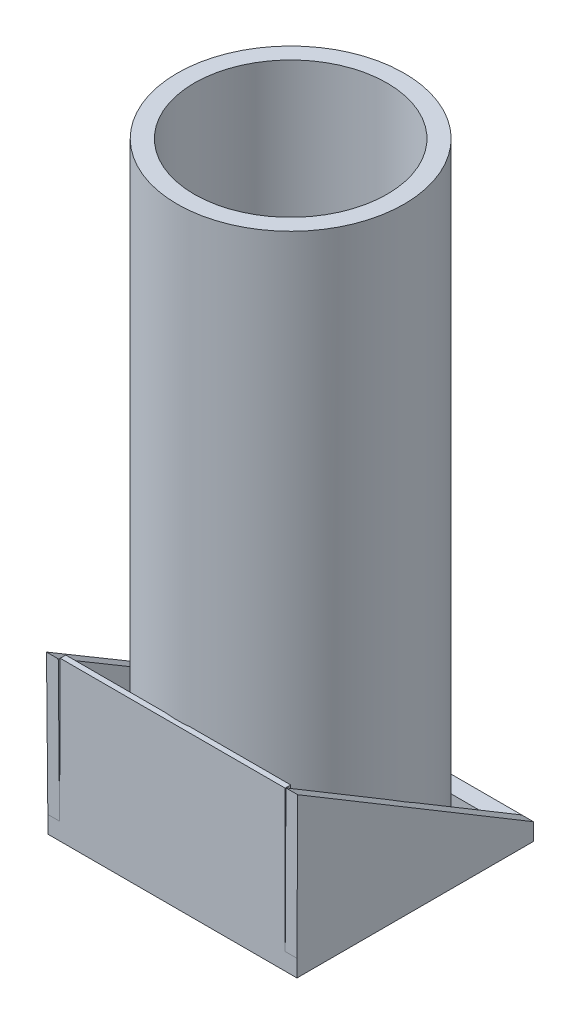
SolidWorks part; units mm, degrees
ref_plane "Front Plane" through (0, 0, 0) normal (0, 0, 1) x (1, 0, 0)
ref_plane "Top Plane" through (0, 0, 0) normal (0, 1, 0) x (1, 0, 0)
ref_plane "Right Plane" through (0, 0, 0) normal (1, 0, 0) x (0, 0, -1)
sketch "Sketch1" plane through (0, 0, 0) normal (0, 1, 0) x (1, 0, 0)
  circle A0 centre (0, 0) radius 135
  dimension "D1" = 270
extrude "Boss-Extrude1" add sketch "Sketch1" along normal blind 700
sketch "Sketch2" plane through (0, 0, 0) normal (0, -1, 0) x (-1, 0, 0)
  line L1 (-148.1806, 140.7055) -> (148.1806, 140.7055)
  line L2 (-148.1806, 140.7055) -> (-148.1806, -140.7055)
  line L3 (-148.1806, -140.7055) -> (148.1806, -140.7055)
  line L4 (148.1806, 140.7055) -> (148.1806, -140.7055)
  line L5 (-148.1806, 140.7055) -> (148.1806, -140.7055) construction
  line L6 (-148.1806, -140.7055) -> (148.1806, 140.7055) construction
  point P0 (0, 0)
extrude "Boss-Extrude2" add sketch "Sketch2" along normal blind 20.32
sketch "Sketch3" plane through (-148.1806, 0, 0) normal (-1, 0, 0) x (0, 0, 1)
  line L0 (-140.7055, 0) -> (142.3005, 168.1079)
  line L1 (142.3005, 168.1079) -> (140.7055, 0)
  line L2 (140.7055, 0) -> (-140.7055, 0)
  dimension "D1" = 168.1079
shell "Shell1" thickness 20.32 removed face at (0, 700, 135)
shell "Shell2" thickness 20.32 removed face at (0, -20.32, 0) removed face at (0, 0, 135)
extrude "Boss-Extrude3" add sketch "Sketch3" against normal blind 13.97 contours L0 L1 L2
sketch "Sketch4" plane through (148.1806, 0, 0) normal (1, 0, 0) x (0, 0, -1)
  line L0 (140.7055, 0) -> (-139.8664, 168.1079)
  line L1 (-139.8664, 168.1079) -> (-140.7055, 0)
  line L2 (-140.7055, 0) -> (140.7055, 0)
extrude "Boss-Extrude4" add sketch "Sketch4" against normal blind 13.97
sketch "Sketch6" plane through (0, 0, 140.7055) normal (0, 0, 1) x (1, 0, 0)
  line L0 (134.1621, 168.2799) -> (-133.5009, 168.2799)
  line L1 (-133.5009, 168.2799) -> (-134.2106, 0)
  line L2 (-134.2106, 0) -> (134.2106, 0)
  line L3 (134.2106, 0) -> (-134.2106, 0) construction
  line L4 (134.2106, 0) -> (134.1621, 168.2799)
extrude "Boss-Extrude5" add sketch "Sketch6" against normal blind 6.604
